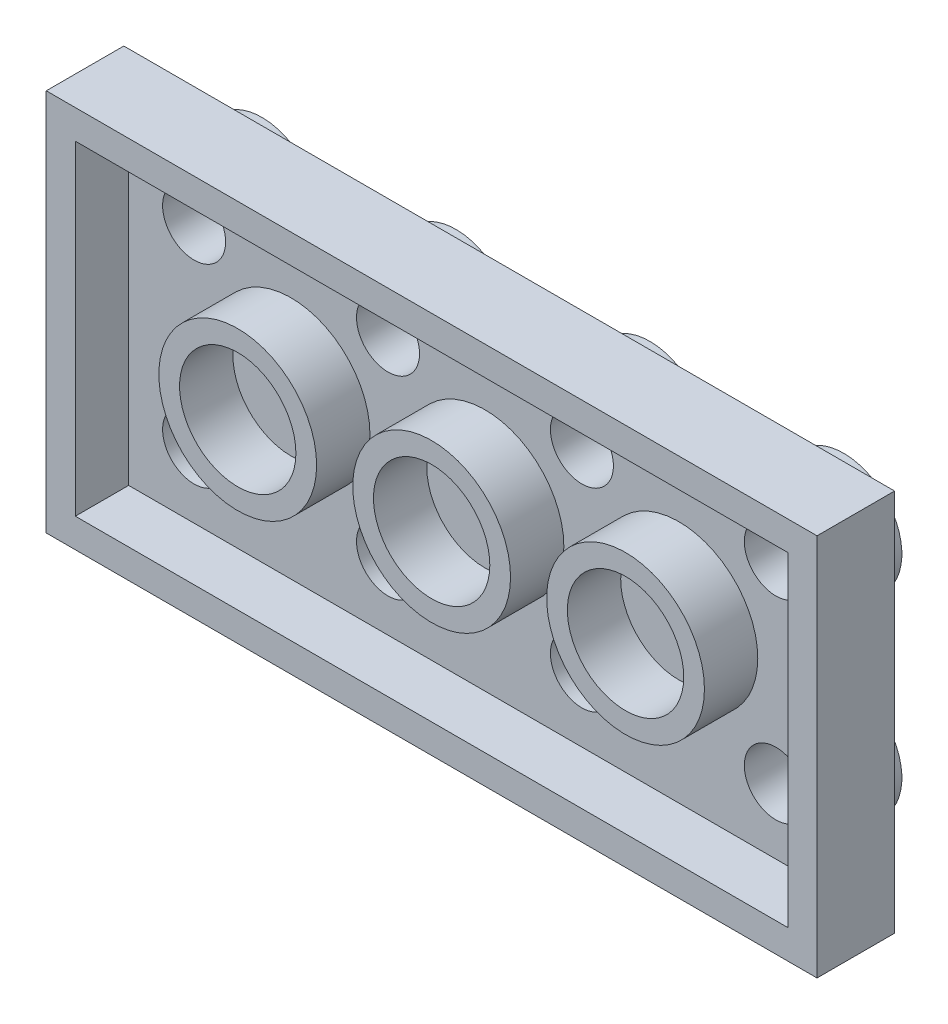
SolidWorks part; units mm, degrees
ref_plane "Front Plane" through (0, 0, 0) normal (0, 0, 1) x (1, 0, 0)
ref_plane "Top Plane" through (0, 0, 0) normal (0, 1, 0) x (1, 0, 0)
ref_plane "Right Plane" through (0, 0, 0) normal (1, 0, 0) x (0, 0, -1)
sketch "Sketch2" plane through (0, 0, 0) normal (0, 0, 1) x (1, 0, 0)
  line L0 (23.9, -7.8) -> (15.9, -7.8) construction
  line L1 (0, 0) -> (31.8, 0)
  line L2 (0, 0) -> (0, -15.8)
  line L3 (0, -15.8) -> (31.8, -15.8)
  line L4 (31.8, 0) -> (31.8, -15.8)
  line L6 (1.2, -1.2) -> (30.6, -1.2)
  line L7 (1.2, -1.2) -> (1.2, -14.6)
  line L8 (1.2, -14.6) -> (30.6, -14.6)
  line L9 (30.6, -1.2) -> (30.6, -14.6)
  circle A0 centre (23.9, -7.8) radius 2.4
  circle A1 centre (15.9, -7.8) radius 2.4
  circle A2 centre (7.9, -7.8) radius 2.4
  circle A3 centre (23.9, -7.8) radius 3.255
  circle A4 centre (15.9, -7.8) radius 3.255
  circle A5 centre (7.9, -7.8) radius 3.255
  dimension "D4" = 4.8
  dimension "D5" = 7.8
  dimension "D7" = 6.51
  dimension "D1" = 15.8
  dimension "D2" = 31.8
  dimension "D3" = 7.9
  dimension "D9" = 8
  dimension "D10" = 7.9
  dimension "D11" = 1.2
  dimension "D12" = 1.2
  dimension "D13" = 1.2
  dimension "D14" = 1.2
  dimension "D6" = 3
  dimension "D8" = 3
extrude "Boss-Extrude1" add sketch "Sketch2" against normal blind 3.2 contours L4 L1 L2 L3 L6 L9 L8 L7 region at (15.9, -0.3551, 0)
extrude "Boss-Extrude2" add sketch "Sketch2<3>" against normal blind 2.2 separate body contours A5 A2 | A4 A1 | A0 A3 region at (20.7371, -7.8, 0) region at (12.7371, -7.8, 0) region at (4.7371, -7.8, 0)
sketch "Sketch2<3>" plane through (0, 0, 0) normal (0, 0, 1) x (1, 0, 0) same geometry as "Sketch2"
sketch "Sketch3" plane through (0, 0, -2.2) normal (0, 0, -1) x (-1, 0, 0)
  line L1 (-30.6, -1.2) -> (-1.2, -1.2)
  line L2 (-30.6, -1.2) -> (-30.6, -14.6)
  line L3 (-30.6, -14.6) -> (-1.2, -14.6)
  line L4 (-1.2, -1.2) -> (-1.2, -14.6)
extrude "Boss-Extrude3" add sketch "Sketch3" along normal blind 1
sketch "Sketch4" plane through (0, 0, -3.2) normal (0, 0, -1) x (-1, 0, 0)
  line L0 (-31.8, 0) -> (-31.8, -15.8) construction
  line L1 (0, 0) -> (-31.8, 0) construction
  line L2 (-27.9, -3.9) -> (-19.9, -3.9) construction
  line L3 (0, -15.8) -> (-31.8, -15.8) construction
  circle A0 centre (-27.9, -3.9) radius 2.4
  circle A1 centre (-19.9, -3.9) radius 2.4
  circle A2 centre (-11.9, -3.9) radius 2.4
  circle A3 centre (-3.9, -3.9) radius 2.4
  circle A4 centre (-19.9, -11.9) radius 2.4
  circle A5 centre (-11.9, -11.9) radius 2.4
  circle A6 centre (-3.9, -11.9) radius 2.4
  circle A7 centre (-27.9, -11.9) radius 2.4
  dimension "D1" = 4.8
  dimension "D2" = 3.9
  dimension "D3" = 3.9
  dimension "D6" = 8
  dimension "D7" = 3.9
  dimension "D8" = 3.9
  dimension "D4" = 4
  dimension "D5" = 2
extrude "Boss-Extrude4" add sketch "Sketch4" along normal blind 1.8
sketch "Sketch5" plane through (0, 0, -2.2) normal (0, 0, 1) x (1, 0, 0)
  line L0 (3.9, -3.9) -> (11.9, -3.9) construction
  line L1 (0, 0) -> (0, -15.8) construction
  line L2 (0, -15.8) -> (31.8, -15.8) construction
  circle A0 centre (3.9, -3.9) radius 1.3
  circle A1 centre (11.9, -3.9) radius 1.3
  circle A2 centre (19.9, -3.9) radius 1.3
  circle A3 centre (27.9, -3.9) radius 1.3
  circle A4 centre (11.9, -11.9) radius 1.3
  circle A5 centre (19.9, -11.9) radius 1.3
  circle A6 centre (27.9, -11.9) radius 1.3
  circle A7 centre (3.9, -11.9) radius 1.3
  dimension "D1" = 2.6
  dimension "D5" = 3.9
  dimension "D6" = 3.9
  dimension "D4" = 8
  dimension "D2" = 4
  dimension "D3" = 2
extrude "Cut-Extrude1" cut sketch "Sketch5" against normal blind 1.8
